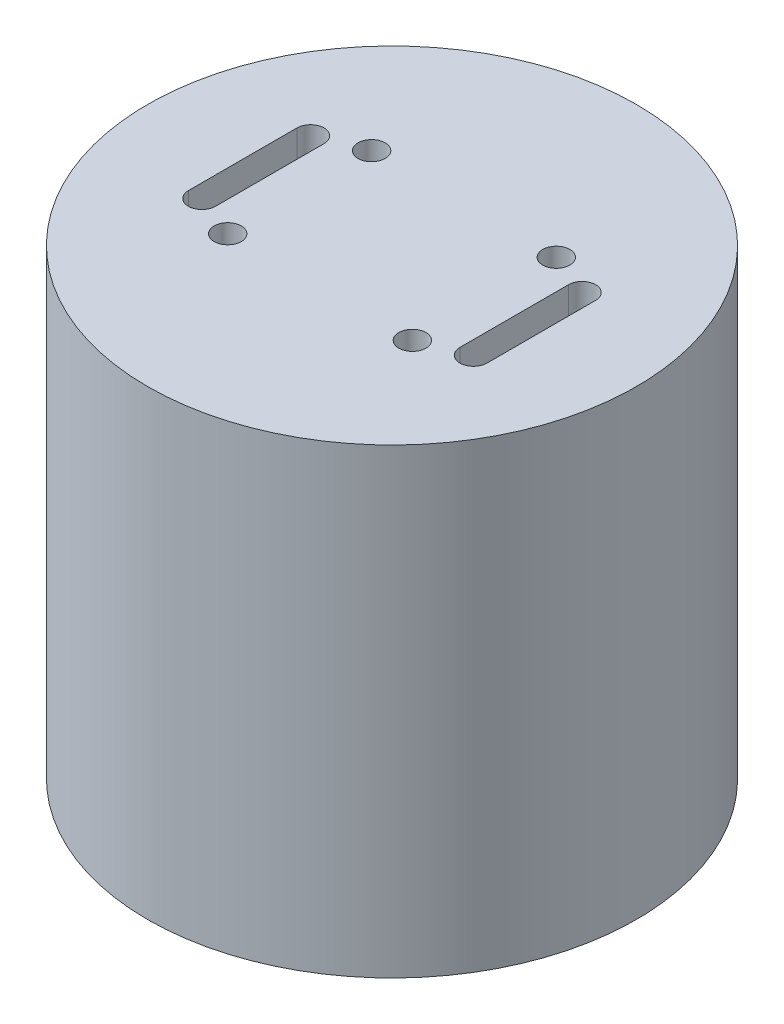
SolidWorks part; units mm, degrees
ref_plane "Front Plane" through (0, 0, 0) normal (0, 0, 1) x (1, 0, 0)
ref_plane "Top Plane" through (0, 0, 0) normal (0, 1, 0) x (1, 0, 0)
ref_plane "Right Plane" through (0, 0, 0) normal (1, 0, 0) x (0, 0, -1)
sketch "Sketch1" plane through (0, 0, 0) normal (0, 1, 0) x (1, 0, 0)
  circle A0 centre (0, 0) radius 90
  dimension "D1" = 180
extrude "Boss-Extrude1" add sketch "Sketch1" along normal blind 10
sketch "Sketch2" plane through (0, 10, 0) normal (0, 1, 0) x (1, 0, 0)
  line L1 (-34, 26.5) -> (34, 26.5) construction
  line L2 (-34, 26.5) -> (-34, -26.5) construction
  line L3 (-34, -26.5) -> (34, -26.5) construction
  line L4 (34, 26.5) -> (34, -26.5) construction
  line L5 (-34, 26.5) -> (34, -26.5) construction
  line L6 (-34, -26.5) -> (34, 26.5) construction
  circle A0 centre (-34, -26.5) radius 5
  circle A1 centre (34, -26.5) radius 5
  circle A2 centre (34, 26.5) radius 5
  circle A3 centre (-34, 26.5) radius 5
  point P0 (0, 0)
  dimension "D3" = 10
  dimension "D1" = 68
  dimension "D2" = 53
extrude "Cut-Extrude1" cut sketch "Sketch2" against normal through all
sketch "Sketch3" plane through (0, 0, 0) normal (0, -1, 0) x (1, 0, 0)
  circle A0 centre (0, 0) radius 90
  circle A1 centre (0, 0) radius 80
  circle A2 centre (0, 0) radius 90 construction
  circle A3 centre (0, 0) radius 90
  circle M7 centre (0, 0) radius 90
  dimension "D2" = 10
extrude "Boss-Extrude2" add sketch "Sketch3" along normal blind 150 contours A1 M7 region at (-87.4544, 0, 0)
sketch "Sketch4" plane through (0, 10, 0) normal (0, 1, 0) x (1, 0, 0)
  line L0 (50, 20) -> (50, -20) construction
  line L1 (55, 20) -> (55, -20)
  line L2 (45, 20) -> (45, -20)
  arc A0 (55, 20) -> (45, 20) centre (50, 20) ccw
  arc A1 (45, -20) -> (55, -20) centre (50, -20) ccw
  point P2 (50, 0)
  dimension "D2" = 5
  dimension "D1" = 50
  dimension "D3" = 20
extrude "Cut-Extrude2" cut sketch "Sketch4" against normal through all
mirror "Mirror1" about plane through (0, 0, 0) normal (1, 0, 0) of "Cut-Extrude2"
sketch "Sketch8" plane through (0, -150, 0) normal (0, -1, 0) x (1, 0, 0)
  circle A0 centre (0, 0) radius 90 construction
  circle A1 centre (0, 0) radius 90
extrude "Boss-Extrude4" add sketch "Sketch8" along normal blind 10
sketch "Sketch9" plane through (0, -160, 0) normal (0, -1, 0) x (1, 0, 0)
  line L0 (0, -99.0098) -> (0, 98.2841) construction
  line L1 (-111.9692, 0) -> (108.5479, 0) construction
  circle A0 centre (6.5, 15.5) radius 1.5
  circle A1 centre (37.5, 15.5) radius 1.5
  circle A2 centre (6.5, -15.5) radius 1.5
  circle A3 centre (37.5, -15.5) radius 1.5
  circle A4 centre (-6.5, -15.5) radius 1.5
  circle A5 centre (-37.5, -15.5) radius 1.5
  circle A6 centre (-37.5, 15.5) radius 1.5
  circle A7 centre (-6.5, 15.5) radius 1.5
  point P13 (0, 0)
  point P14 (0, 0)
  point P15 (0, 0)
  point P16 (0, 0)
  point P17 (37.5, 15.9538)
  dimension "D1" = 3
  dimension "D4" = 5
  dimension "D2" = 31
  dimension "D3" = 31
extrude "Cut-Extrude3" cut sketch "Sketch9" against normal up to next
